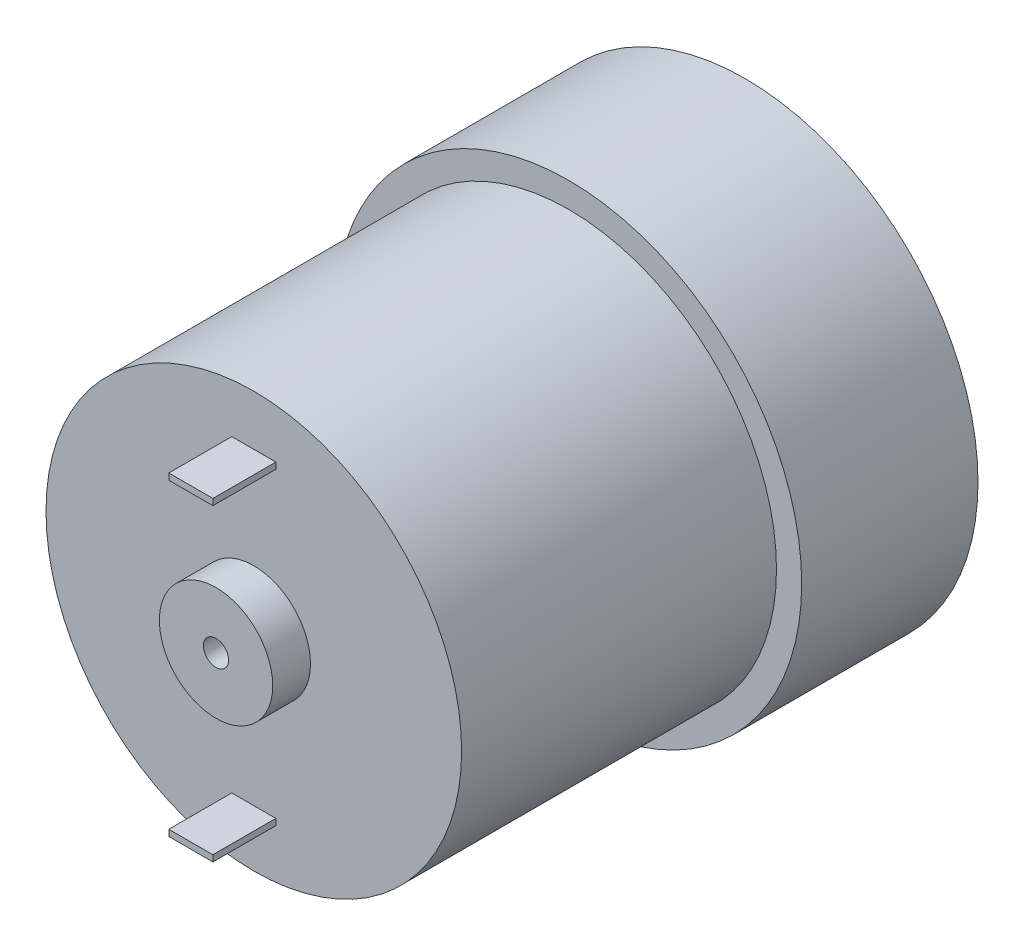
SolidWorks part; units mm, degrees
material "6063-O"
ref_plane "Front Plane" through (0, 0, 0) normal (0, 0, 1) x (1, 0, 0)
ref_plane "Top Plane" through (0, 0, 0) normal (0, 1, 0) x (1, 0, 0)
ref_plane "Right Plane" through (0, 0, 0) normal (1, 0, 0) x (0, 0, -1)
sketch "Sketch1" plane through (0, 0, 0) normal (0, 0, 1) x (1, 0, 0)
  circle A0 centre (0, 0) radius 18.5
  dimension "D1" = 37
extrude "Boss-Extrude1" add sketch "Sketch1" along normal blind 42
sketch "Sketch2" plane through (0, 0, 42) normal (0, 0, 1) x (1, 0, 0)
  circle A0 centre (0, 0) radius 18.5
  circle A1 centre (0, 0) radius 18.5 construction
  circle A2 centre (0, 0) radius 4.5
  dimension "D1" = 9
extrude "Cut-Extrude1" cut sketch "Sketch2" against normal blind 3
sketch "Sketch3" plane through (0, 0, 39) normal (0, 0, 1) x (1, 0, 0)
  circle A0 centre (0, 0) radius 18.5
  circle A1 centre (0, 0) radius 18.5 construction
  circle A2 centre (0, 0) radius 16.5
  circle M4 centre (0, 0) radius 18.5
  dimension "D1" = 33
extrude "Cut-Extrude4" cut sketch "Sketch3" against normal blind 25 contours A2 M4 region at (-17.9767, 0, 39)
sketch "Sketch4" plane through (0, 0, 0) normal (0, 0, -1) x (-1, 0, 0)
  line L0 (0, 0) -> (0, -18.5) construction
  circle A0 centre (0, 0) radius 18.5 construction
  circle A1 centre (0, -7) radius 6
  dimension "D2" = 12
  dimension "D1" = 7
extrude "Boss-Extrude2" add sketch "Sketch4" along normal blind 4.6
fillet "Fillet1" radius 0.5 1 edges at (-6, -7, -4.6)
sketch "Sketch5" plane through (0, 0, -4.6) normal (0, 0, -1) x (-1, 0, 0)
  circle A0 centre (0, -7) radius 3
  dimension "D1" = 6
extrude "Cut-Extrude5" cut sketch "Sketch5" against normal blind 10
sketch "Sketch6" plane through (0, 0, 42) normal (0, 0, 1) x (1, 0, 0)
  circle A0 centre (0, 0) radius 1
  dimension "D1" = 2
extrude "Cut-Extrude6" cut sketch "Sketch6" against normal blind 10
sketch "Sketch7" plane through (0, 0, 39) normal (0, 0, 1) x (1, 0, 0)
  line L0 (0, -16.5) -> (0, 16.5) construction
  line L2 (1.75, 12) -> (-1.75, 12)
  line L3 (1.75, 12) -> (1.75, 12.5)
  line L4 (1.75, 12.5) -> (-1.75, 12.5)
  line L5 (-1.75, 12) -> (-1.75, 12.5)
  line L6 (1.75, 12) -> (-1.75, 12.5) construction
  line L7 (1.75, 12.5) -> (-1.75, 12) construction
  line L8 (-1.75, -12) -> (1.75, -12)
  line L9 (-1.75, -12) -> (-1.75, -12.5)
  line L10 (-1.75, -12.5) -> (1.75, -12.5)
  line L11 (1.75, -12) -> (1.75, -12.5)
  line L12 (-1.75, -12) -> (1.75, -12.5) construction
  line L13 (-1.75, -12.5) -> (1.75, -12) construction
  circle A0 centre (0, 0) radius 16.5 construction
  point P5 (0, 12.25)
  point P10 (0, -12.25)
  dimension "D1" = 3.5
  dimension "D2" = 0.5
  dimension "D3" = 12
  dimension "D4" = 12
extrude "Boss-Extrude3" add sketch "Sketch7" along normal blind 5
sketch "Sketch8" plane through (0, 0, 0) normal (0, 0, -1) x (-1, 0, 0)
  line L0 (0, 0) -> (15.5, 0) construction
  line L1 (0, 0) -> (-15.5, 0) construction
  line L2 (0, 0) -> (-7.75, 13.4234) construction
  line L3 (0, 0) -> (-7.75, -13.4234) construction
  line L4 (-13.8293, -7) -> (13.8293, -7) construction
  circle A0 centre (0, 0) radius 15.5 construction
  circle A1 centre (-7.75, 13.4234) radius 1.5
  circle A2 centre (15.5, 0) radius 1.75
  circle A3 centre (-7.75, -13.4234) radius 1.5
  circle A4 centre (-13.8293, -7) radius 1.5
  circle A5 centre (-15.5, 0) radius 1.75
  circle A6 centre (13.8293, -7) radius 1.5
  circle A7 centre (0, 15.5) radius 1.75
  point P15 (0, -7)
  dimension "D1" = 31
  dimension "D4" = 3
  dimension "D5" = 3.5
  dimension "D2" = 120
  dimension "D3" = 120
hole_wizard "M3x0.5 Tapped Hole1" positions "Sketch9" profile "Sketch10" tap size "M3x0.5" standard "ANSI Metric"
sketch "Sketch9" plane through (0, 0, 0) normal (0, 0, -1) x (-1, 0, 0)
  point P0 (-7.75, 13.4234)
  point P3 (-13.8293, -7)
  point P6 (13.8293, -7)
  point P9 (-7.75, -13.4234)
  point P12 (0, 0)
sketch "Sketch10" plane through (7.75, 13.4234, 0) normal (1, 0, 0) x (0, 1, 0)
  line L0 (0, 0) -> (0, 8.2511)
  line L1 (0, 8.2511) -> (1.25, 7.5)
  line L2 (1.25, 7.5) -> (1.25, 0)
  line L5 (1.25, 0) -> (0, 0)
  line L10 (0, 8.2511) -> (-1.25, 7.5) construction
  line L11 (0, -6.35) -> (0, 107.95) construction
  dimension "Tap Drill Dia." = 2.5
  dimension "Tap Drill Depth" = 7.5
  dimension "Drill Angle" = 118
cosmetic thread "Hole Thread1" parameters "D1"=6, "D2"=3
cosmetic thread "Hole Thread2" parameters "D1"=6, "D2"=3
cosmetic thread "Hole Thread3" parameters "D1"=6, "D2"=3
cosmetic thread "Hole Thread4" parameters "D1"=6, "D2"=3
hole_wizard "Ø3.0mm Dowel Hole1" positions "Sketch11" profile "Sketch12" hole size "Ø3.0" standard "ANSI Metric"
sketch "Sketch11" plane through (0, 0, 0) normal (0, 0, -1) x (-1, 0, 0)
  point P0 (-15.5, 0)
  point P3 (0, 15.5)
  point P6 (15.5, 0)
sketch "Sketch12" plane through (15.5, 0, 0) normal (1, 0, 0) x (0, 1, 0)
  line L0 (0, 0) -> (0, 8.4013)
  line L1 (0, 8.4013) -> (1.5, 7.5)
  line L2 (1.5, 7.5) -> (1.5, 0)
  line L5 (1.5, 0) -> (0, 0)
  line L10 (0, 8.4013) -> (-1.5, 7.5) construction
  line L11 (0, -6.35) -> (0, 107.95) construction
  dimension "Hole Dia." = 3
  dimension "Hole Depth" = 7.5
  dimension "Drill Angle" = 118
equation "\"D4@Sketch7\"=\"D3@Sketch7\""
